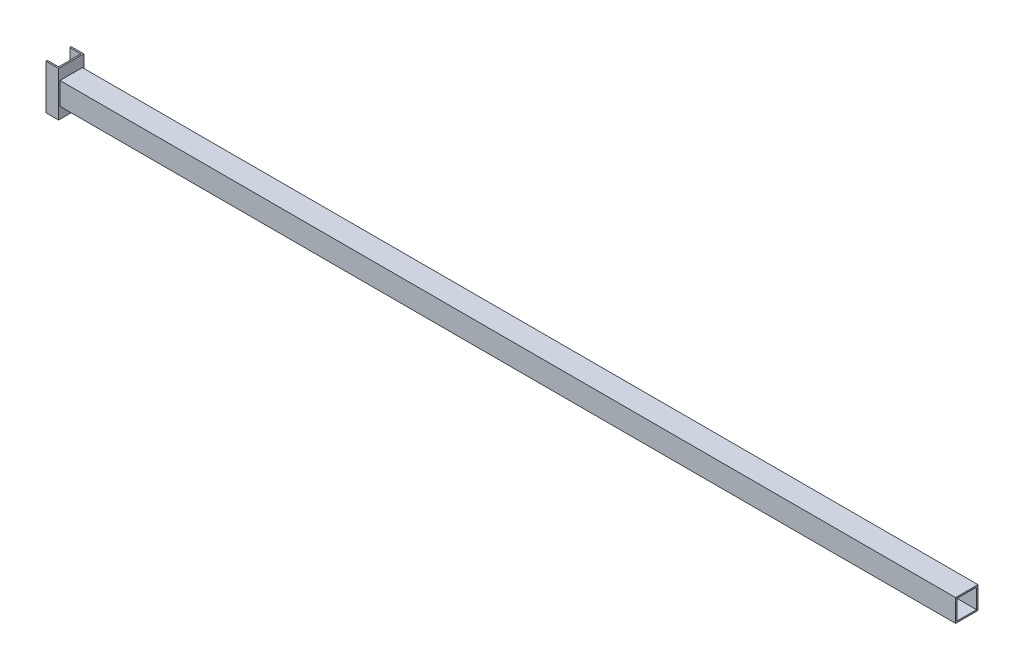
SolidWorks part; units mm, degrees
note: The reader was unsure of these and kept them because the rebuilt part matched: shared geometry of "Sketch1<3>", "Sketch1<4>".
material "6061-T4 (SS)"
ref_plane "Front Plane" through (0, 0, 0) normal (0, 0, 1) x (1, 0, 0)
ref_plane "Top Plane" through (0, 0, 0) normal (0, 1, 0) x (1, 0, 0)
ref_plane "Right Plane" through (0, 0, 0) normal (1, 0, 0) x (0, 0, -1)
sketch "Sketch1" plane through (0, 0, 0) normal (1, 0, 0) x (0, 0, -1)
  line L0 (-12.7, 25.4) -> (-12.7, -25.4)
  line L1 (-14.2875, -25.4) -> (14.2875, -25.4)
  line L2 (-14.2875, -25.4) -> (-14.2875, 25.4)
  line L3 (-14.2875, 25.4) -> (14.2875, 25.4)
  line L4 (14.2875, -25.4) -> (14.2875, 25.4)
  line L5 (-14.2875, -25.4) -> (14.2875, 25.4) construction
  line L6 (-14.2875, 25.4) -> (14.2875, -25.4) construction
  line L7 (12.7, 25.4) -> (12.7, -25.4)
  line L8 (-11.1125, 11.1125) -> (11.1125, 11.1125)
  line L9 (-12.7, -12.7) -> (12.7, -12.7)
  line L10 (-12.7, -12.7) -> (-12.7, 12.7)
  line L11 (-12.7, 12.7) -> (12.7, 12.7)
  line L12 (12.7, -12.7) -> (12.7, 12.7)
  line L13 (-12.7, -12.7) -> (12.7, 12.7) construction
  line L14 (-12.7, 12.7) -> (12.7, -12.7) construction
  line L15 (11.1125, -11.1125) -> (11.1125, 11.1125)
  line L16 (-11.1125, -11.1125) -> (11.1125, -11.1125)
  line L17 (-11.1125, -11.1125) -> (-11.1125, 11.1125)
  point P0 (0, 0)
  point P10 (0, 0)
  dimension "D1" = 50.8
  dimension "D2" = 28.575
  dimension "D3" = 1.5875
  dimension "D4" = 1.5875
  dimension "D5" = 25.4
  dimension "D6" = 25.4
  dimension "D7" = 1.5875
extrude "Boss-Extrude1" add sketch "Sketch1" against normal blind 1.5875 contours L0 L11 L7 L3 | L11 L0 L9 L7 | L9 L0 L1 L7 | L3 L2 L1 L0 | L3 L7 L1 L4 | L17 L16 L15 L8
extrude "Boss-Extrude2" add sketch "Sketch1<3>" against normal blind 14.2875 contours L3 L2 L1 L0 | L3 L7 L1 L4
sketch "Sketch1<3>" plane through (0, 0, 0) normal (1, 0, 0) x (0, 0, -1) same geometry as "Sketch1"
extrude "Boss-Extrude3" add sketch "Sketch1<4>" along normal blind 1016 contours L11 L0 L9 L7 L16 L17 L8 L15
sketch "Sketch1<4>" plane through (0, 0, 0) normal (1, 0, 0) x (0, 0, -1) same geometry as "Sketch1"
sketch3d "3DSketch1"
  line L0 (-1.5875, 25.4, 0) -> (-1.5875, -25.4, 0) construction
  line L1 (-1.5875, 25.4, 12.7) -> (-1.5875, 25.4, -12.7) construction
  line L2 (-1.5875, -25.4, 12.7) -> (-1.5875, -25.4, -12.7) construction
  line L5 (-1.5875, 12.7, -6.35) -> (-4.7625, 12.7, -6.35)
  line L6 (-4.7625, 12.7, -6.35) -> (-1.5875, 19.05, -6.35)
  line L7 (-1.5875, 19.05, -6.35) -> (-1.5875, 12.7, -6.35)
  dimension "D1" = 6.35
  dimension "D2" = 6.35
  dimension "D3" = 6.35
  dimension "D4" = 3.175
extrude "Boss-Extrude4" add sketch "3DSketch1" along direction (0, 0, -1) on the side of the normal blind 12.7
pattern_linear "LPattern1" count 2 spacing 25.4 along (0, -1, 0) of "Boss-Extrude4"
